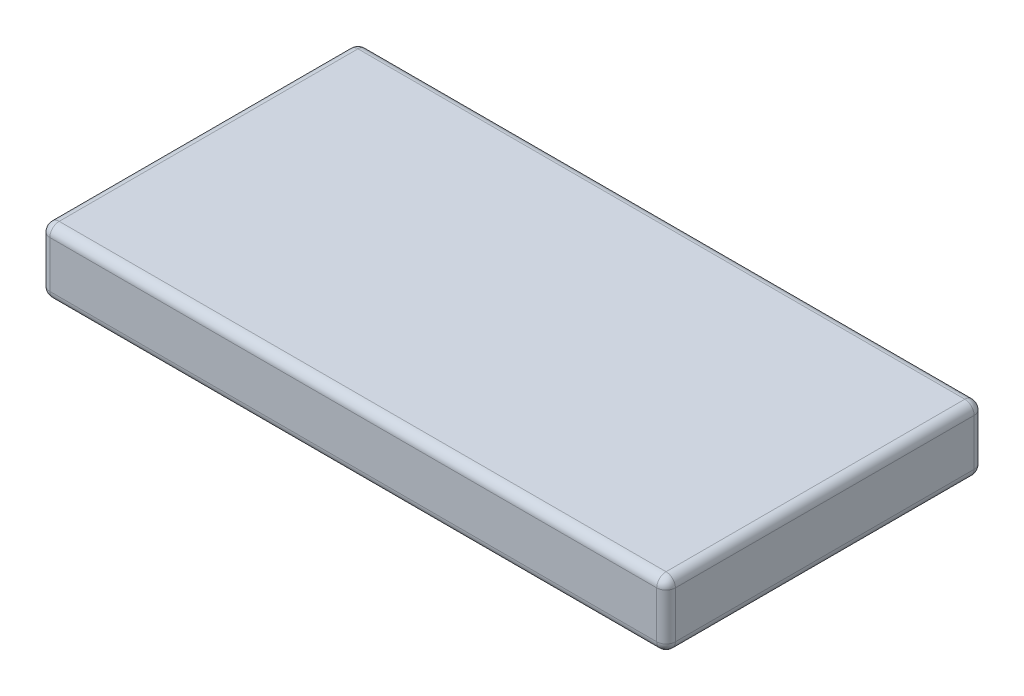
SolidWorks part; units mm, degrees
ref_plane "Front Plane" through (0, 0, 0) normal (0, 0, 1) x (1, 0, 0)
ref_plane "Top Plane" through (0, 0, 0) normal (0, 1, 0) x (1, 0, 0)
ref_plane "Right Plane" through (0, 0, 0) normal (1, 0, 0) x (0, 0, -1)
sketch "Sketch1" plane through (0, 0, 0) normal (0, 1, 0) x (1, 0, 0)
  line L1 (-33.5, 17) -> (33.5, 17)
  line L2 (-33.5, 17) -> (-33.5, -17)
  line L3 (-33.5, -17) -> (33.5, -17)
  line L4 (33.5, 17) -> (33.5, -17)
  line L5 (-33.5, 17) -> (33.5, -17) construction
  line L6 (-33.5, -17) -> (33.5, 17) construction
  point P0 (0, 0)
  dimension "D1" = 34
  dimension "D2" = 67
extrude "Boss-Extrude1" add sketch "Sketch1" along normal blind 7
fillet "Fillet1" radius 1 12 edges at (-33.5, 3.5, -17) (33.5, 3.5, -17) (-33.5, 7, 0) (0, 7, -17) (33.5, 7, 0) (-33.5, 3.5, 17) (0, 7, 17) (33.5, 3.5, 17) (0, 0, -17) (-33.5, 0, 0) (0, 0, 17) (33.5, 0, 0)
